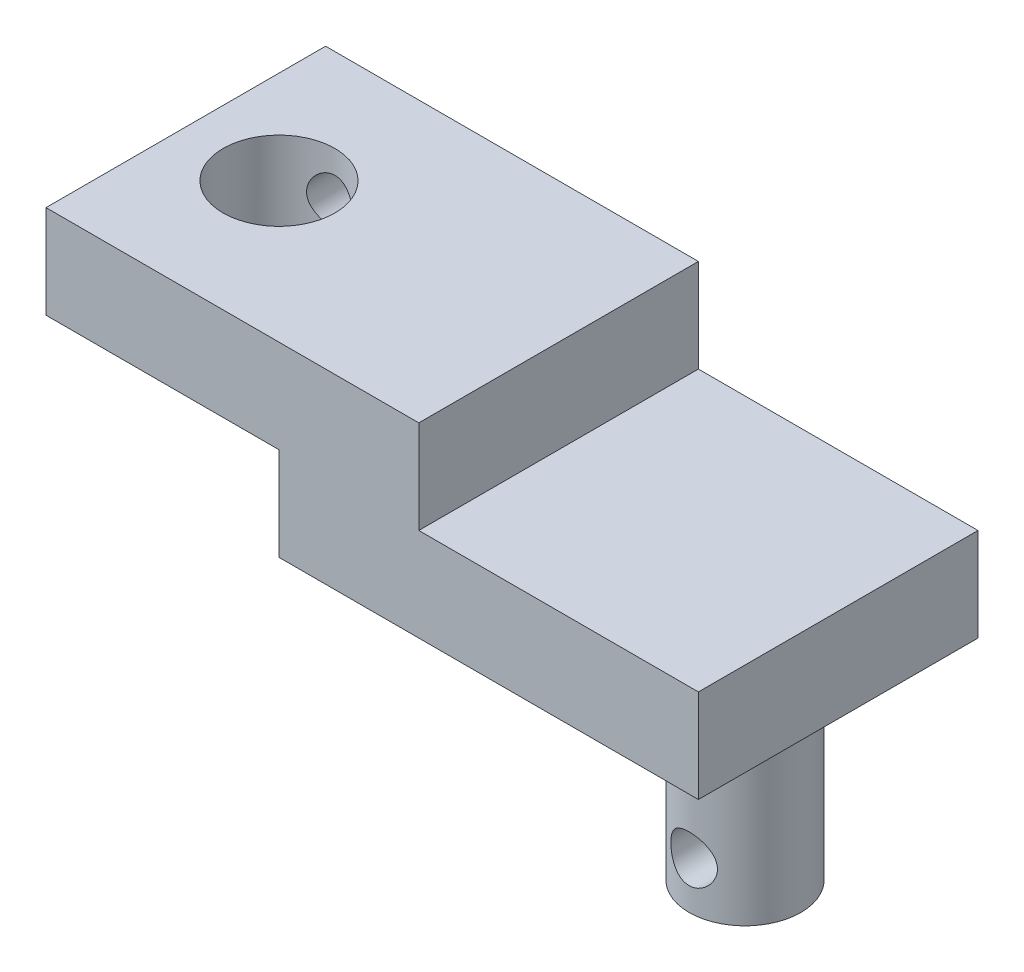
SolidWorks part; units mm, degrees
ref_plane "前视基准面" through (0, 0, 0) normal (0, 0, 1) x (1, 0, 0)
ref_plane "上视基准面" through (0, 0, 0) normal (0, 1, 0) x (1, 0, 0)
ref_plane "右视基准面" through (0, 0, 0) normal (1, 0, 0) x (0, 0, -1)
sketch "草图1" plane through (0, 0, 0) normal (0, 0, 1) x (1, 0, 0)
  line L0 (-123.4203, 0) -> (104.1605, 0) construction
  line L1 (0, 79.9874) -> (0, -92.1722) construction
  line L3 (-40, 10) -> (0, 10)
  line L4 (-40, 10) -> (-40, 0)
  line L5 (-40, 0) -> (-15, 0)
  line L6 (0, 10) -> (0, 0)
  line L7 (0, 0) -> (30, 0)
  line L8 (-15, 0) -> (-15, -10)
  line L9 (-15, -10) -> (30, -10)
  line L10 (30, 0) -> (30, -10)
  dimension "D1" = 10
  dimension "D2" = 40
  dimension "D3" = 10
  dimension "D4" = 30
  dimension "D5" = 25
extrude "凸台-拉伸1" add sketch "草图1" along normal mid plane 30
sketch "草图2" plane through (0, 10, 0) normal (0, 1, 0) x (1, 0, 0)
  line L0 (-40, 0) -> (0, 0) construction
  line L1 (-40, -15) -> (-40, 15) construction
  circle A0 centre (-30, 0) radius 6
  dimension "D2" = 12
  dimension "D3" = 10
extrude "切除-拉伸1" cut sketch "草图2" against normal up to next
sketch "草图3" plane through (0, -10, 0) normal (0, -1, 0) x (1, 0, 0)
  line L0 (-15, 0) -> (30, 0) construction
  line L1 (30, 15) -> (30, -15) construction
  line L2 (-15, 15) -> (-15, -15) construction
  circle A0 centre (20, 0) radius 6
  dimension "D3" = 12
  dimension "D2" = 10
extrude "凸台-拉伸2" add sketch "草图3" along normal blind 20
sketch "草图4" plane through (0, 0, 0) normal (0, 0, 1) x (1, 0, 0)
  line L0 (-30, 10) -> (-30, 0) construction
  line L1 (0, 10) -> (-40, 10) construction
  line L2 (-40, 0) -> (-15, 0) construction
  line L3 (-36, 10) -> (-36, 0) construction
  line L4 (-24, 0) -> (-24, 10) construction
  circle A0 centre (-30, 5) radius 2.5
  dimension "D1" = 5
extrude "切除-拉伸2" cut sketch "草图4" against normal through all
ref_axis "基准轴1" through (20, -30, 0) along (0, 1, 0)
ref_plane "基准面1" through (0, 0, 0) normal (0, 0, -1) x (-1, 0, 0)
sketch "草图5" plane through (0, 0, 0) normal (0, 0, -1) x (-1, 0, 0)
  line L0 (-20, -30) -> (-20, -10) construction
  line L1 (-26, -30) -> (-14, -30) construction
  circle A0 centre (-20, -25) radius 2.5
  dimension "D1" = 5
  dimension "D2" = 5
extrude "切除-拉伸3" cut sketch "草图5" against normal through all and the other way through all
